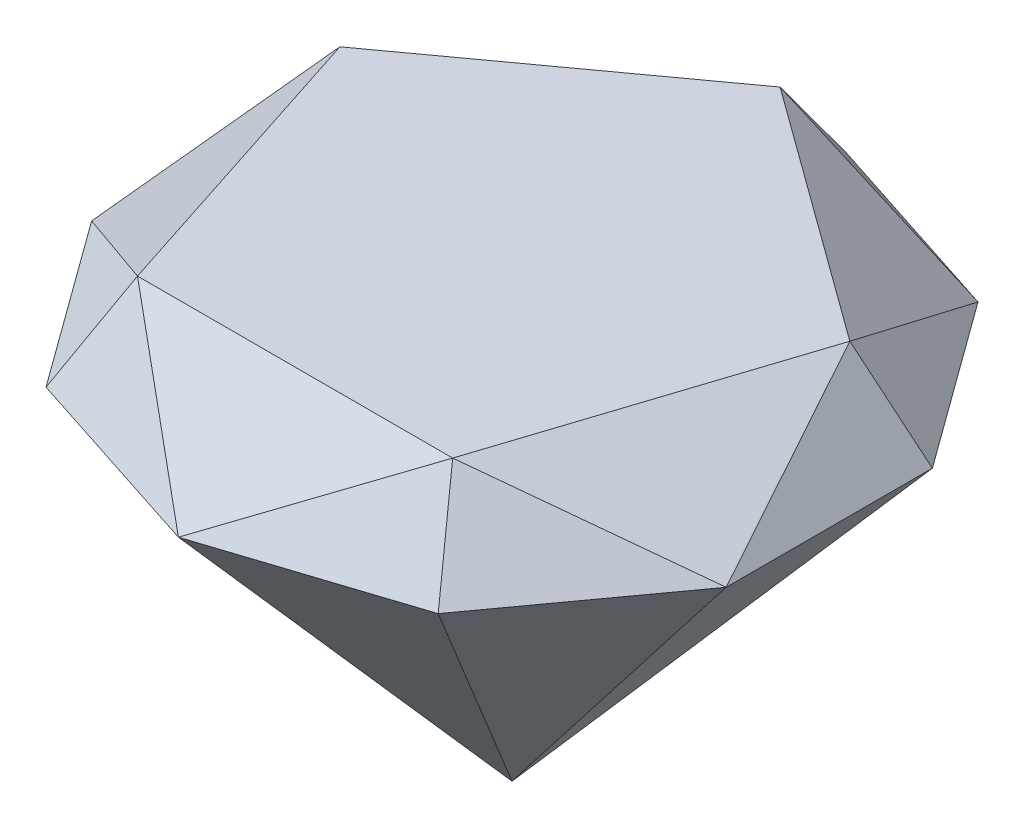
SolidWorks part; units mm, degrees
ref_plane "Front Plane" through (0, 0, 0) normal (0, 0, 1) x (1, 0, 0)
ref_plane "Top Plane" through (0, 0, 0) normal (0, 1, 0) x (1, 0, 0)
ref_plane "Right Plane" through (0, 0, 0) normal (1, 0, 0) x (0, 0, -1)
sketch "Sketch3" plane through (0, 0, 0) normal (0, 1, 0) x (1, 0, 0)
  line L1 (0, -75) -> (44.0839, -60.6763)
  line L2 (44.0839, -60.6763) -> (71.3292, -23.1763)
  line L3 (71.3292, -23.1763) -> (71.3292, 23.1763)
  line L4 (71.3292, 23.1763) -> (44.0839, 60.6763)
  line L5 (44.0839, 60.6763) -> (0, 75)
  line L6 (0, 75) -> (-44.0839, 60.6763)
  line L7 (-44.0839, 60.6763) -> (-71.3292, 23.1763)
  line L8 (-71.3292, 23.1763) -> (-71.3292, -23.1763)
  line L9 (-71.3292, -23.1763) -> (-44.0839, -60.6763)
  line L10 (-44.0839, -60.6763) -> (0, -75)
  circle A0 centre (0, 0) radius 71.3292 construction
  dimension "D1" = 150
extrude "Boss-Extrude1" add sketch "Sketch3" along normal blind 90 draft 40
extrude "Boss-Extrude2" add sketch "Sketch3<2>" against normal blind 20 draft 35
sketch "Sketch3<2>" plane through (0, 0, 0) normal (0, 1, 0) x (1, 0, 0) same geometry as "Sketch3"
sketch3d "3DSketch4"
  line L0 (-35.4289, -20, 48.7636) -> (-57.3251, -20, -18.6261)
  line L1 (-57.3251, -20, -18.6261) -> (-71.3292, 0, 23.1763)
  line L2 (-71.3292, 0, 23.1763) -> (-35.4289, -20, 48.7636)
ref_plane "Plane1" through (-26.2156, -36.1599, 8.518) normal (0.5766, 0.7953, -0.1873) x (0.817, -0.5612, 0.1322)
sketch "Sketch7" plane through (-26.2156, -36.1599, 8.518) normal (0.5766, 0.7953, -0.1873) x (0.817, -0.5612, 0.1322)
  line L0 (-11.2763, -42.8787) -> (-55.2154, -22.5588)
  line L1 (-55.2154, -22.5588) -> (-38.0755, 22.7156)
  line L2 (-38.0755, 22.7156) -> (-11.2763, -42.8787)
extrude "Cut-Extrude1" cut sketch "Sketch7" against normal blind 20
sketch "Sketch8" plane through (0, 0, 0) normal (0, 0, 1) x (1, 0, 0)
  line L0 (0, -40.3869) -> (0, 109.7246)
pattern_circular "CirPattern1" count 5 over 360 about axis through (0, -40.3869, 0) along (0, 1, 0) of "Cut-Extrude1"
move or copy body "Body-Move/Copy2" bodies to move or copy 104 copy yes number of copies 1 rotation origin (0, 32.5034, 0) rotation axis (0, 0, 1) rotation angle 180
delete or keep bodies "Body-Delete/Keep 1" type delete bodies bodies 104
